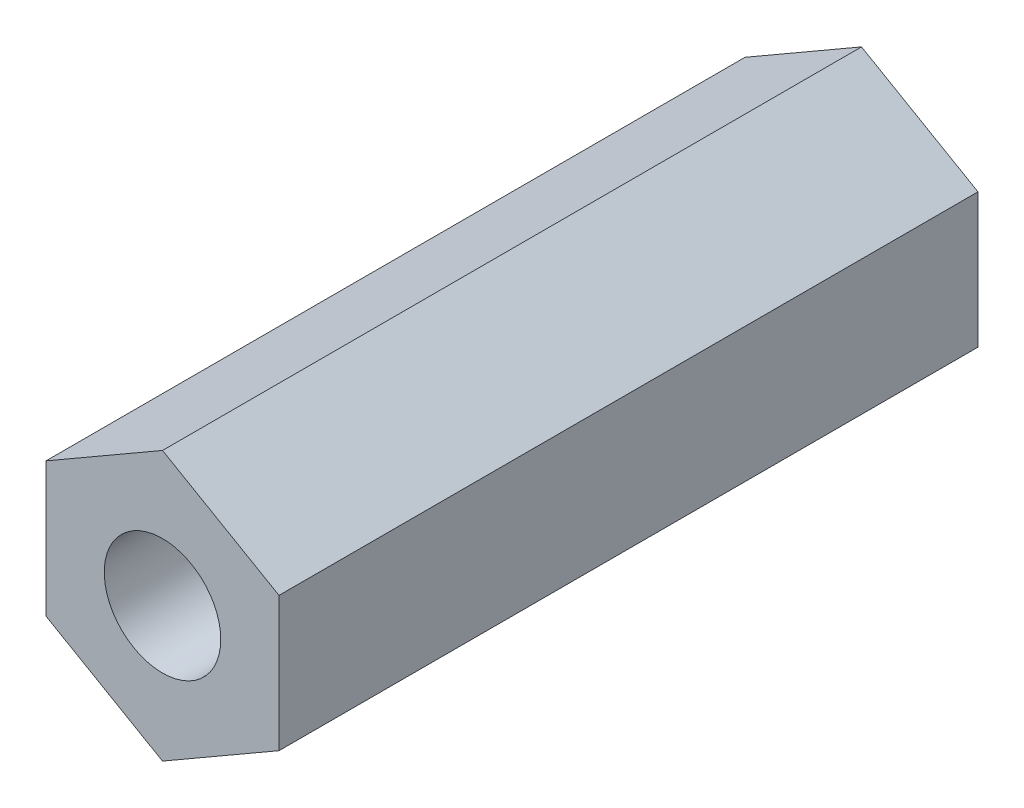
SolidWorks part; units mm, degrees
ref_plane "Front Plane" through (0, 0, 0) normal (0, 0, 1) x (1, 0, 0)
ref_plane "Top Plane" through (0, 0, 0) normal (0, 1, 0) x (1, 0, 0)
ref_plane "Right Plane" through (0, 0, 0) normal (1, 0, 0) x (0, 0, -1)
sketch "Sketch3" plane through (0, 0, 0) normal (1, 0, 0) x (0, 0, -1)
  line L0 (-9, 0) -> (9, 0) construction
  line L1 (0, 3) -> (0, -3) construction
  line L2 (-9, 1.5) -> (-9, -1.5) construction
  point P2 (-3.7, 0)
  point P3 (3.7, 0)
  dimension "D1" = 12.7
sketch "Sketch1" plane through (0, 0, 0) normal (0, 0, 1) x (1, 0, 0)
  line L1 (0, 3.4641) -> (-3, 1.7321)
  line L2 (-3, 1.7321) -> (-3, -1.7321)
  line L3 (-3, -1.7321) -> (0, -3.4641)
  line L4 (0, -3.4641) -> (3, -1.7321)
  line L5 (3, -1.7321) -> (3, 1.7321)
  line L6 (3, 1.7321) -> (0, 3.4641)
  circle A0 centre (0, 0) radius 3 construction
  circle A1 centre (0, 0) radius 1.5
extrude "Extrude1" add sketch "Sketch1" along normal up to vertex (9 mm away) and the other way up to vertex (9 mm away) up to point (0, 0, 9) other way up to point (0, 0, -9)
sketch "Sketch11" plane through (0, 0, -9) normal (0, 0, -1) x (-1, 0, 0)
  circle A0 centre (0, 0) radius 1.5 construction
  circle A1 centre (0, 0) radius 1.5
curve "Helix/Spiral1" pitch 0.5 height 18.5 turns 37 parameters "Pitch"=0.5
sketch "Sketch12" plane through (0, 0, 0) normal (1, 0, 0) x (0, 0, -1)
  line L0 (9.4375, 1.5) -> (9, 1.5)
  line L1 (9.4375, 1.5) -> (9.25, 1.1752)
  line L2 (9.25, 1.1752) -> (9.1875, 1.1752)
  line L3 (9.1875, 1.1752) -> (9, 1.5)
  line L4 (9.2188, 1.1752) -> (9.2188, 1.5) construction
  line L5 (9.3438, 1.3376) -> (9.0938, 1.3376) construction
  dimension "D1" = 0.0625
  dimension "D2" = 0.25
  dimension "D3" = 60
sweep "Sweep1" [suppressed] add profiles "Sketch12" path "Helix/Spiral1"
sketch "Sketch6" plane through (0, 0, -9) normal (0, 0, -1) x (-1, 0, 0)
  line L6 (0, 3.4641) -> (-3, 1.7321)
  line L7 (-3, 1.7321) -> (-3, -1.7321)
  line L8 (-3, -1.7321) -> (0, -3.4641)
  line L9 (0, -3.4641) -> (3, -1.7321)
  line L10 (3, -1.7321) -> (3, 1.7321)
  line L11 (3, 1.7321) -> (0, 3.4641)
  line L12 (0, 3.4641) -> (-3, 1.7321)
  line L13 (-3, 1.7321) -> (-3, -1.7321)
  line L14 (-3, -1.7321) -> (0, -3.4641)
  line L15 (0, -3.4641) -> (3, -1.7321)
  line L16 (3, -1.7321) -> (3, 1.7321)
  line L17 (3, 1.7321) -> (0, 3.4641)
  dimension "D1" = 0
extrude "Extrude2" [suppressed] cut sketch "Sketch6" along normal through all
sketch "Sketch7" plane through (0, 0, -9) normal (0, 0, -1) x (-1, 0, 0)
  circle A2 centre (0, 0) radius 1.5508
  circle A3 centre (0, 0) radius 1.5508
  dimension "D1" = 0.0508
extrude "Extrude3" [suppressed] cut sketch "Sketch7" against normal through all draft 43
sketch "Sketch8" plane through (0, 0, -9) normal (0, 0, -1) x (-1, 0, 0)
  circle A0 centre (0, 0) radius 3 construction
  circle A1 centre (0, 0) radius 3
extrude "Extrude4" [suppressed] cut sketch "Sketch8" against normal through all draft 60 flip side to cut
mirror "Mirror1" [suppressed] about plane through (0, 0, 0) normal (0, 0, 1)
sketch "Sketch9" [suppressed] plane through (0, 0, 0) normal (1, 0, 0) x (0, 0, -1)
  line L1 (-12.7, 2.4638) -> (12.7, 2.4638)
  line L2 (-12.7, 2.4638) -> (-12.7, 0)
  line L3 (-12.7, 0) -> (12.7, 0)
  line L4 (12.7, 2.4638) -> (12.7, 0)
  line L7 (-25.4, 0) -> (25.4, 0) construction
revolve "Revolve" [suppressed] add sketch "Sketch9" angle 360 about L0
sketch "Sketch10" [suppressed] plane through (0, 0, 0) normal (1, 0, 0) x (0, 0, -1)
  line L0 (25.4, 2.413) -> (12.7, 2.413)
  line L1 (-25.4, 2.413) -> (-12.7, 2.413)
  line L2 (12.7, 2.413) -> (12.7, -2.413)
  line L3 (-25.4, -2.4638) -> (-12.7, -2.4638)
  line L4 (-12.7, 2.413) -> (-12.7, -2.4638)
  line L5 (12.7, -2.413) -> (25.4, -2.413)
sketch "Sketch13" [suppressed] plane through (0, 0, 9) normal (0, 0, 1) x (1, 0, 0)
  line L0 (0.6959, 0.4402) -> (1.0897, 0.4402) construction
  line L1 (0.6959, 0.4402) -> (0.6959, -0.3853) construction
  line L2 (0.6959, 0.4402) -> (3.8103, 3.3481) construction
  arc A0 (0.5013, -1.063) -> (1.1082, -0.3912) centre (0, 0) ccw construction
  point P0 (0.6959, 0.4402)
  point P8 (-11.7542, 6.7404)
  point P9 (3.8103, 3.3481)
  point P10 (3.8103, 3.3481)
  point P11 (1.0897, 0.4402)
equation "\"D1@Sketch3\" = \"Min Thread Length@Sketch3\""
equation "\"D3@Helix/Spiral1\" = \"Length@Sketch3\"+\"Pitch@Helix/Spiral1\""
equation "\"D1@Sketch12\" = \"Pitch@Helix/Spiral1\"*.125"
equation "\"D2@Sketch12\" = \"Pitch@Helix/Spiral1\"*.5"
